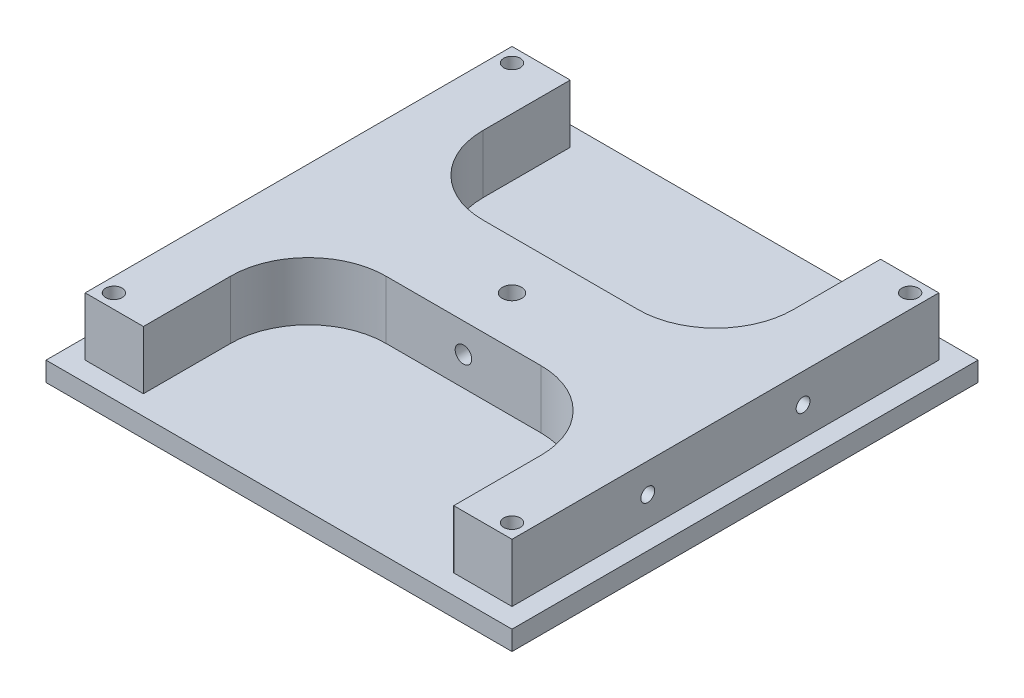
SolidWorks part; units mm, degrees
material "6061-T6 (SS)"
ref_plane "Front Plane" through (0, 0, 0) normal (0, 0, 1) x (1, 0, 0)
ref_plane "Top Plane" through (0, 0, 0) normal (0, 1, 0) x (1, 0, 0)
ref_plane "Right Plane" through (0, 0, 0) normal (1, 0, 0) x (0, 0, -1)
sketch "Sketch1" plane through (0, 0, 0) normal (0, 1, 0) x (1, 0, 0)
  line L1 (-38.1, -38.1) -> (38.1, -38.1)
  line L2 (-38.1, -38.1) -> (-38.1, 38.1)
  line L3 (-38.1, 38.1) -> (38.1, 38.1)
  line L4 (38.1, -38.1) -> (38.1, 38.1)
  line L5 (-38.1, -38.1) -> (38.1, 38.1) construction
  line L6 (-38.1, 38.1) -> (38.1, -38.1) construction
  point P0 (0, 0)
  dimension "D1" = 76.2
  dimension "D2" = 76.2
extrude "Boss-Extrude1" add sketch "Sketch1" along normal blind 3.175
sketch "Sketch2" plane through (0, 3.175, 0) normal (0, 1, 0) x (1, 0, 0)
  line L0 (-38.1, 38.1) -> (-38.1, -38.1) construction
  line L1 (34.8971, -34.8971) -> (-34.8971, -34.8971)
  line L2 (34.8971, -34.8971) -> (34.8971, 34.8971)
  line L3 (34.8971, 34.8971) -> (-34.8971, 34.8971)
  line L4 (-34.8971, -34.8971) -> (-34.8971, 34.8971)
  line L5 (38.1, -38.1) -> (38.1, 38.1) construction
  line L6 (-38.1, -38.1) -> (38.1, -38.1) construction
  line L14 (38.1, 38.1) -> (-38.1, 38.1) construction
  point P0 (0, 0)
  point P6 (0, 0)
  dimension "D1" = 3.2029
  dimension "D2" = 3.2029
  dimension "D3" = 3.2029
  dimension "D4" = 3.2029
extrude "Boss-Extrude2" add sketch "Sketch2" along normal blind 9.525
sketch "Sketch8" plane through (34.8971, 0, 0) normal (1, 0, 0) x (0, 0, -1)
  line L0 (-38.1, 3.175) -> (38.1, 3.175) construction
  point P0 (-12.7, 7.9375)
  dimension "D1" = 4.7625
  dimension "D2" = 12.7
hole_wizard "#4-40 Tapped Hole1" positions "Sketch10" profile "Sketch9" tap size "#4-40" standard "ANSI Inch"
sketch "Sketch10" plane through (34.8971, 0, 0) normal (1, 0, 0) x (0, 0, -1)
  point P0 (-12.7, 7.9375)
sketch "Sketch9" plane through (34.8971, 7.9375, 12.7) normal (0, 1, 0) x (0, 0, -1)
  line L0 (0, 0) -> (0, 7.2832)
  line L1 (0, 7.2832) -> (1.1303, 6.604)
  line L2 (1.1303, 6.604) -> (1.1303, 0)
  line L5 (1.1303, 0) -> (0, 0)
  line L10 (0, 7.2832) -> (-1.1303, 6.604) construction
  line L11 (0, -6.35) -> (0, 107.95) construction
  dimension "Tap Drill Dia." = 2.2606
  dimension "Tap Drill Depth" = 6.604
  dimension "Drill Angle" = 118
cosmetic thread "Hole Thread1" parameters "D1"=2.4486, "D2"=2.8448
mirror "Mirror1" about plane through (0, 0, 0) normal (0, 0, 1) of "#4-40 Tapped Hole1"
mirror "Mirror2" about plane through (0, 0, 0) normal (1, 0, 0) of "Mirror1"
sketch "Sketch11" plane through (0, 0, 0) normal (0, -1, 0) x (1, 0, 0)
  circle A0 centre (32.5501, -32.5501) radius 2.032
  dimension "D1" = 4.064
hole_wizard "#6-32 Tapped Hole1" positions "Sketch13" profile "Sketch12" tap size "#6-32" standard "ANSI Inch" end condition through all
sketch "Sketch13" plane through (0, 0, 0) normal (0, -1, 0) x (-1, 0, 0)
  point P0 (-32.5501, 32.5501)
sketch "Sketch12" plane through (32.5501, 0, -32.5501) normal (1, 0, 0) x (0, 0, -1)
  line L0 (0, 0) -> (0, 12.7)
  line L1 (0, 12.7) -> (1.3525, 12.7)
  line L2 (1.3525, 12.7) -> (1.3525, 0)
  line L5 (1.3525, 0) -> (0, 0)
  line L11 (0, -6.35) -> (0, 107.95) construction
  dimension "Thru Tap Drill Dia." = 2.7051
  dimension "Thru Tap Drill Depth" = 12.7
cosmetic thread "Hole Thread2" parameters "D2"=3.5052
ref_axis "Axis1" through (0, -0.635, 0) along (0, 1, 0)
pattern_circular "CirPattern1" count 4 over 360 about axis through (0, -0.635, 0) along (0, 1, 0) of "#6-32 Tapped Hole1"
sketch "Sketch14" plane through (0, 0, 0) normal (0, -1, 0) x (1, 0, 0)
  circle A0 centre (0, 0) radius 3.175
  dimension "D1" = 6.35
extrude "Cut-Extrude1" cut sketch "Sketch14" against normal through all
sketch "Sketch15" plane through (0, 12.7, 0) normal (0, 1, 0) x (1, 0, 0)
  line L0 (-25.3721, -7.9375) -> (25.3721, -7.9375)
  line L1 (25.3721, -7.9375) -> (25.3721, -34.8971)
  line L2 (-34.8971, -34.8971) -> (34.8971, -34.8971) construction
  line L3 (-25.3721, -7.9375) -> (-25.3721, -34.8971)
  line L4 (-34.8971, 34.8971) -> (-34.8971, -34.8971) construction
  line L5 (34.8971, -34.8971) -> (34.8971, 34.8971) construction
  line L6 (-25.3721, -34.8971) -> (25.3721, -34.8971)
  dimension "D1" = 9.525
  dimension "D2" = 9.525
  dimension "D3" = 7.9375
extrude "Cut-Extrude2" cut sketch "Sketch15" against normal blind 9.525
fillet "Fillet1" radius 12.7 2 edges at (25.3721, 7.9375, 7.9375) (-25.3721, 7.9375, 7.9375)
sketch "Sketch16" plane through (0, 0, 7.9375) normal (0, 0, 1) x (1, 0, 0)
  line L0 (12.6721, 3.175) -> (-12.6721, 3.175) construction
  point P0 (0, 7.9375)
  dimension "D1" = 4.7625
hole_wizard "#6-32 Tapped Hole2" positions "Sketch18" profile "Sketch17" tap size "#6-32" standard "ANSI Inch"
sketch "Sketch18" plane through (0, 0, 7.9375) normal (0, 0, 1) x (1, 0, 0)
  point P0 (0, 7.9375)
sketch "Sketch17" plane through (0, 7.9375, 7.9375) normal (1, 0, 0) x (0, -1, 0)
  line L0 (0, 0) -> (0, 10.4647)
  line L1 (0, 10.4647) -> (1.3525, 9.652)
  line L2 (1.3525, 9.652) -> (1.3525, 0)
  line L5 (1.3525, 0) -> (0, 0)
  line L10 (0, 10.4647) -> (-1.3526, 9.652) construction
  line L11 (0, -6.35) -> (0, 107.95) construction
  dimension "Tap Drill Dia." = 2.7051
  dimension "Tap Drill Depth" = 9.652
  dimension "Drill Angle" = 118
cosmetic thread "Hole Thread3" parameters "D1"=6.35, "D2"=3.5052
mirror "Mirror3" about plane through (0, 0, 0) normal (0, 0, 1) of "Fillet1", "Cut-Extrude2", "#6-32 Tapped Hole2"
sketch "Sketch20" plane through (0, 12.7, 0) normal (0, 1, 0) x (1, 0, 0)
  circle A0 centre (0, 0) radius 1.5875
  circle M5 centre (0, 0) radius 3.175
  dimension "D1" = 3.175
extrude "Boss-Extrude3" add sketch "Sketch20" against normal blind 2.54 contours A0 M5 region at (-3.0852, 12.7, 0)
equation "\"D2@Sketch2\"=\"D1@Sketch2\""
equation "\"D2@Sketch1\"=\"D1@Sketch1\""
equation "\"D3@Sketch2\"=\"D2@Sketch2\""
equation "\"D4@Sketch2\"=\"D2@Sketch2\""
equation "\"D2@Sketch15\"=\"D1@Sketch15\""
